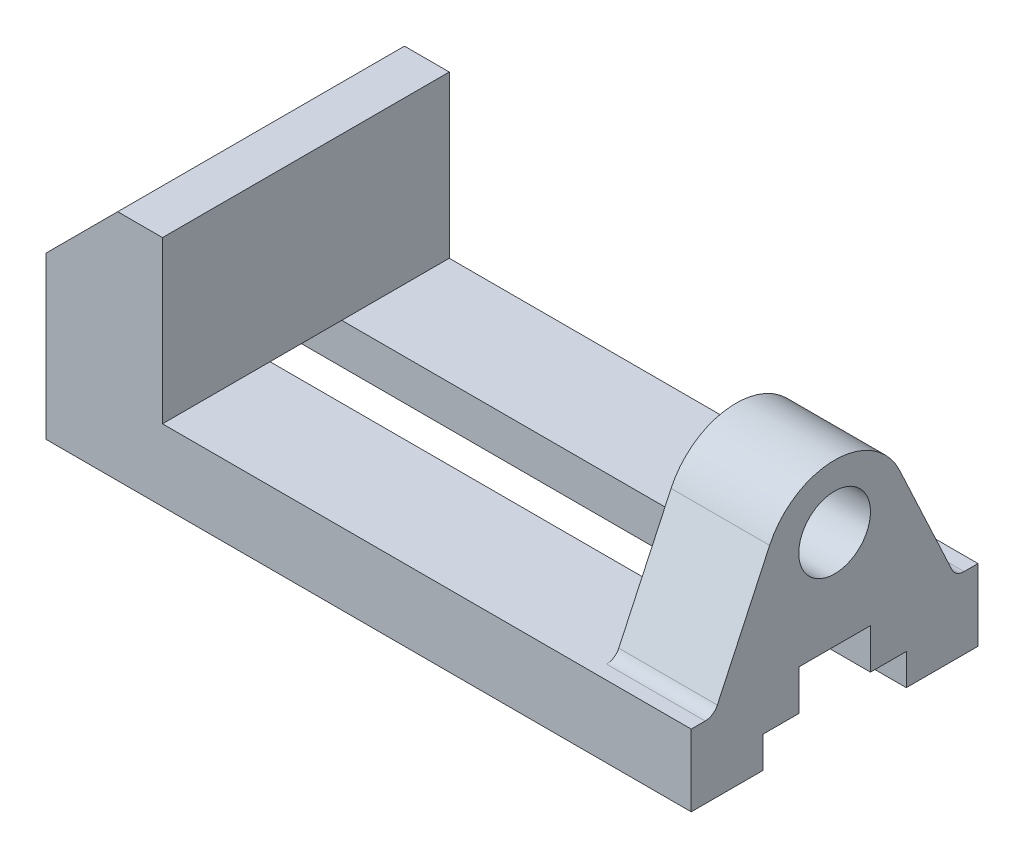
SolidWorks part; units mm, degrees
ref_plane "Front Plane" through (0, 0, 0) normal (0, 0, 1) x (1, 0, 0)
ref_plane "Top Plane" through (0, 0, 0) normal (0, 1, 0) x (1, 0, 0)
ref_plane "Right Plane" through (0, 0, 0) normal (1, 0, 0) x (0, 0, -1)
sketch "Sketch1" plane through (0, 0, 0) normal (0, 0, 1) x (1, 0, 0)
  line L0 (0, 0) -> (144, 0)
  line L1 (0, 0) -> (0, 16)
  line L2 (0, 16) -> (0, 36)
  line L3 (0, 52) -> (26, 52) construction
  line L4 (26, 52) -> (16, 52)
  line L5 (16, 52) -> (0, 36)
  line L6 (26, 52) -> (26, 16)
  line L7 (26, 16) -> (122, 16)
  line L8 (144, 16) -> (144, 52)
  line L9 (144, 0) -> (144, 16)
  line L10 (144, 52) -> (122, 52)
  line L11 (122, 16) -> (122, 52)
  dimension "D1" = 144
  dimension "D2" = 16
  dimension "D3" = 16
  dimension "D4" = 26
  dimension "D5" = 10
  dimension "D6" = 135
  dimension "D7" = 22
  dimension "D8" = 36
  dimension "D9" = 16
extrude "Boss-Extrude1" add sketch "Sketch1" along normal blind 64
sketch "Sketch4" plane through (144, 0, 0) normal (1, 0, 0) x (0, 0, -1)
  line L0 (-64, 0) -> (0, 0) construction
  line L1 (-32, 52) -> (-32, 38) construction
  line L2 (-64, 52) -> (0, 52) construction
  line L3 (-46.5009, 42.7619) -> (-58.1725, 17.7321)
  line L4 (-17.4991, 42.7619) -> (-5.8275, 17.7321)
  line L5 (-32, 0) -> (-32, 16) construction
  line L7 (-64, 16) -> (-64, 52)
  line L8 (-64, 52) -> (0, 52)
  line L9 (0, 52) -> (0, 16)
  line L10 (0, 16) -> (-3.1086, 16)
  line L11 (-64, 16) -> (-60.8914, 16)
  line L12 (-32, 16) -> (-32, 38) construction
  line L13 (-40, 16) -> (-24, 16)
  line L14 (-48, 0) -> (-16, 0)
  line L15 (-48, 0) -> (-48, 7)
  line L16 (-48, 7) -> (-40, 7)
  line L17 (-40, 7) -> (-40, 16)
  line L18 (-24, 7) -> (-24, 16)
  line L19 (-16, 7) -> (-24, 7)
  line L20 (-16, 0) -> (-16, 7)
  arc A1 (-17.4991, 42.7619) -> (-46.5009, 42.7619) centre (-32, 36) ccw
  circle A2 centre (-32, 38) radius 8
  arc A3 (-58.1725, 17.7321) -> (-60.8914, 16) centre (-60.8914, 19) cw
  arc A4 (-5.8275, 17.7321) -> (-3.1086, 16) centre (-3.1086, 19) ccw
  point P25 (-58.9802, 16)
  point P28 (-5.0198, 16)
  point P32 (-32, 16)
  line M7 (0, 0) -> (0, 52)
  line M8 (0, 52) -> (-64, 52)
  line M9 (-64, 52) -> (-64, 0)
  line M10 (-64, 0) -> (0, 0)
  dimension "D2" = 32
  dimension "D5" = 16
  dimension "D6" = 3
  dimension "D1" = 16
  dimension "D3" = 50
  dimension "D4" = 38
  dimension "D7" = 16
  dimension "D8" = 16
  dimension "D9" = 7
  dimension "D10" = 32
extrude "Cut-Extrude1" cut sketch "Sketch4" against normal blind 22 contours A2 | A2 L4 L10 M7 M8 | A2 L8 L11 L3 M9 region at (144, 38.2208, 8.1386) region at (144, 38.2208, 55.8614) region at (144, 38, 32)
extrude "Cut-Extrude2" cut sketch "Sketch4<3>" against normal through all contours L20 L19 L18 L13 L17 L16 L15 M10 region at (144, 6.6304, 32)
sketch "Sketch4<3>" plane through (144, 0, 0) normal (1, 0, 0) x (0, 0, -1) same geometry as "Sketch4"
sketch "Sketch6" plane through (0, 16, 0) normal (0, 1, 0) x (1, 0, 0)
  line L0 (144, -32) -> (0, -32) construction
  line L1 (144, -46.5009) -> (144, -17.4991) construction
  line L2 (0, -64) -> (0, 0) construction
  line L3 (36, -54) -> (36, -10) construction
  line L4 (106, -54) -> (144, -54) construction
  line L5 (144, -46.5009) -> (144, -58.1725) construction
  line L6 (106, -54) -> (36, -54) construction
  point P9 (35.9845, -32)
  dimension "D1" = 144
  dimension "D2" = 38
  dimension "D3" = 70
  dimension "D4" = 44
hole_wizard "Tap Drill for M6x1.0 Tap2" positions "Sketch9" profile "Sketch10" hole size "M6x1.0" standard "ANSI Metric"
sketch "Sketch9" plane through (0, 0, 0) normal (0, -1, 0) x (-1, 0, 0)
  point P0 (-36, -54)
  point P3 (-106, -54)
  point P6 (-106, -10)
  point P8 (-36, -10)
sketch "Sketch10" plane through (36, 0, 54) normal (1, 0, 0) x (0, 0, -1)
  line L0 (0, 0) -> (0, 11.5022)
  line L1 (0, 11.5022) -> (2.5, 10)
  line L2 (2.5, 10) -> (2.5, 0.025)
  line L3 (2.5, 0.025) -> (2.525, 0)
  line L5 (2.525, 0) -> (0, 0)
  line L6 (-2.5, 0.025) -> (-2.525, 0) construction
  line L10 (0, 11.5022) -> (-2.5, 10) construction
  line L11 (0, -6.35) -> (0, 107.95) construction
  dimension "Hole Dia." = 5
  dimension "Hole Depth" = 10
  dimension "Near C'Sink Dia." = 5.05
  dimension "Near C'Sink Angle" = 90
  dimension "Drill Angle" = 118
